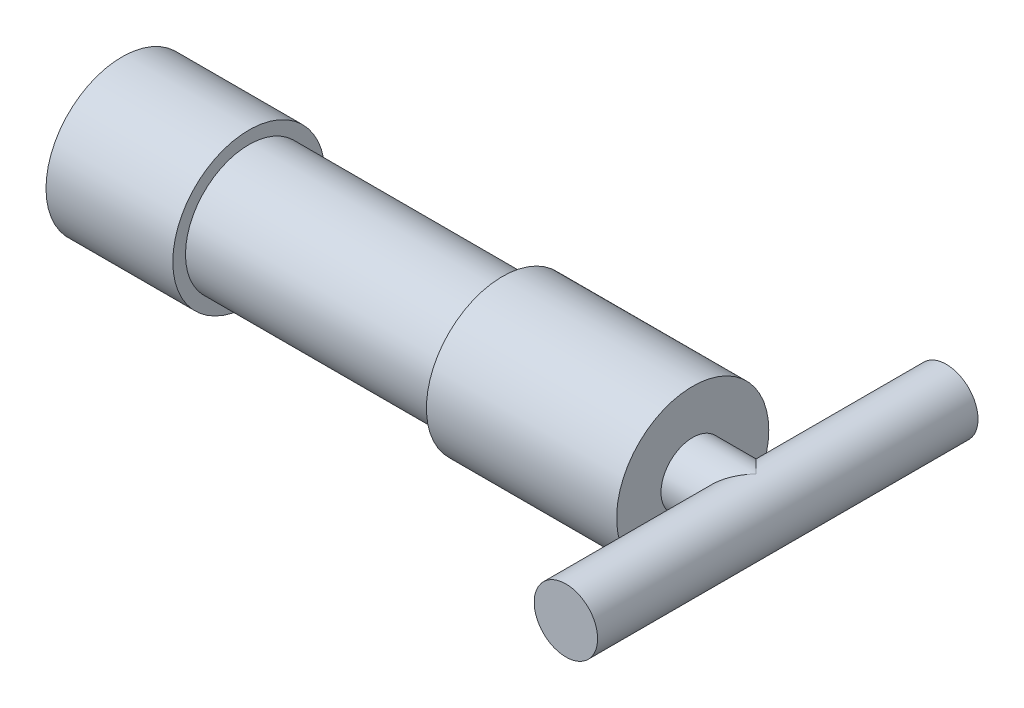
SolidWorks part; units mm, degrees
ref_plane "Front Plane" through (0, 0, 0) normal (0, 0, 1) x (1, 0, 0)
ref_plane "Top Plane" through (0, 0, 0) normal (0, 1, 0) x (1, 0, 0)
ref_plane "Right Plane" through (0, 0, 0) normal (1, 0, 0) x (0, 0, -1)
sketch "Sketch1" plane through (0, 0, 0) normal (1, 0, 0) x (0, 0, -1)
  circle A0 centre (0, 0) radius 5
  dimension "D1" = 10
extrude "Boss-Extrude2" add sketch "Sketch1" along normal blind 35
sketch "Sketch3" plane through (35, 0, 0) normal (1, 0, 0) x (0, 0, -1)
  circle A0 centre (0, 0) radius 2.5
  dimension "D1" = 5
extrude "Boss-Extrude3" add sketch "Sketch3" along normal blind 5
sketch "Sketch4" plane through (35, 0, 0) normal (1, 0, 0) x (0, 0, -1)
  circle A0 centre (0, 0) radius 6
  dimension "D1" = 12
extrude "Boss-Extrude4" add sketch "Sketch4" against normal blind 15
sketch "Sketch6" plane through (0, 0, 0) normal (0, 0, 1) x (1, 0, 0)
  line L0 (40, -2.5) -> (40, 2.5) construction
  circle A0 centre (40, 0) radius 2.5
extrude "Boss-Extrude5" add sketch "Sketch6" along normal blind 15 and the other way blind 15
sketch "Sketch7" plane through (0, 0, 0) normal (-1, 0, 0) x (0, 0, 1)
  circle A0 centre (0, 0) radius 6
  dimension "D1" = 12
extrude "Boss-Extrude6" add sketch "Sketch7" along normal blind 10
sketch3d "3DSketch1"
  line L0 (0, -5, 0) -> (20, -5, 0) construction
  circle A0 centre (0, 0, 0) radius 5 construction
  circle A1 centre (20, 0, 0) radius 5 construction
  point P4 (-5, 0, 0)
  point P7 (25, 0, 0)
